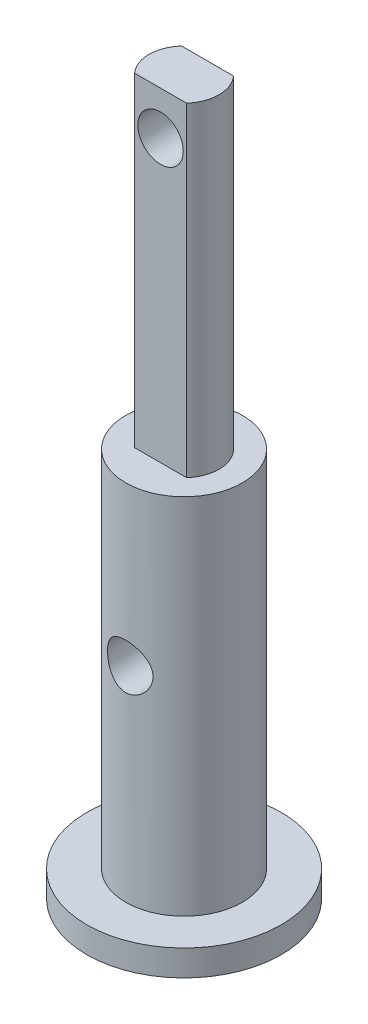
SolidWorks part; units mm, degrees
ref_plane "Front Plane" through (0, 0, 0) normal (0, 0, 1) x (1, 0, 0)
ref_plane "Top Plane" through (0, 0, 0) normal (0, 1, 0) x (1, 0, 0)
ref_plane "Right Plane" through (0, 0, 0) normal (1, 0, 0) x (0, 0, -1)
sketch "Sketch1" plane through (0, 0, 0) normal (0, 1, 0) x (1, 0, 0)
  circle A0 centre (0, 0) radius 7.5
  circle A1 centre (0, 0) radius 4.5
  dimension "D1" = 15
  dimension "D2" = 9
extrude "Boss-Extrude1" add sketch "Sketch1" along normal blind 2
extrude "Boss-Extrude2" add sketch "Sketch1<2>" along normal blind 55 contours A1 region at (0, 0, 0)
sketch "Sketch1<2>" plane through (0, 0, 0) normal (0, 1, 0) x (1, 0, 0) same geometry as "Sketch1"
sketch "Sketch2" plane through (0, 55, 0) normal (0, 1, 0) x (1, 0, 0)
  line L0 (-2, 1.8114) -> (2, 1.8114)
  line L1 (-3.8308, 0) -> (3.4281, 0) construction
  line L2 (-2, -1.8114) -> (2, -1.8114)
  arc A0 (-2, 1.8114) -> (-2, -1.8114) centre (0, 0) ccw
  arc A1 (2, -1.8114) -> (2, 1.8114) centre (0, 0) ccw
  circle A2 centre (0, 0) radius 4.5
extrude "Cut-Extrude1" cut sketch "Sketch2" against normal blind 25
sketch "Sketch3" plane through (0, 0, -1.8114) normal (0, 0, -1) x (-1, 0, 0)
  line L0 (0, 58.9249) -> (0, -1.0204) construction
  line L1 (4.5, 2) -> (-4.5, 2) construction
  circle A0 centre (0, 51.6608) radius 1.75
  circle A1 centre (0, 17.75) radius 1.75
  dimension "D1" = 15.75
extrude "Cut-Extrude2" cut sketch "Sketch3" against normal blind 25 and the other way blind 25 contours A1 L0 | L0 A1 | L0 A0 | A0 L0 region at (-0.7427, 51.6608, -1.8114) region at (-0.7427, 17.75, -1.8114) region at (0.7427, 17.75, -1.8114) region at (0.7427, 51.6608, -1.8114)
